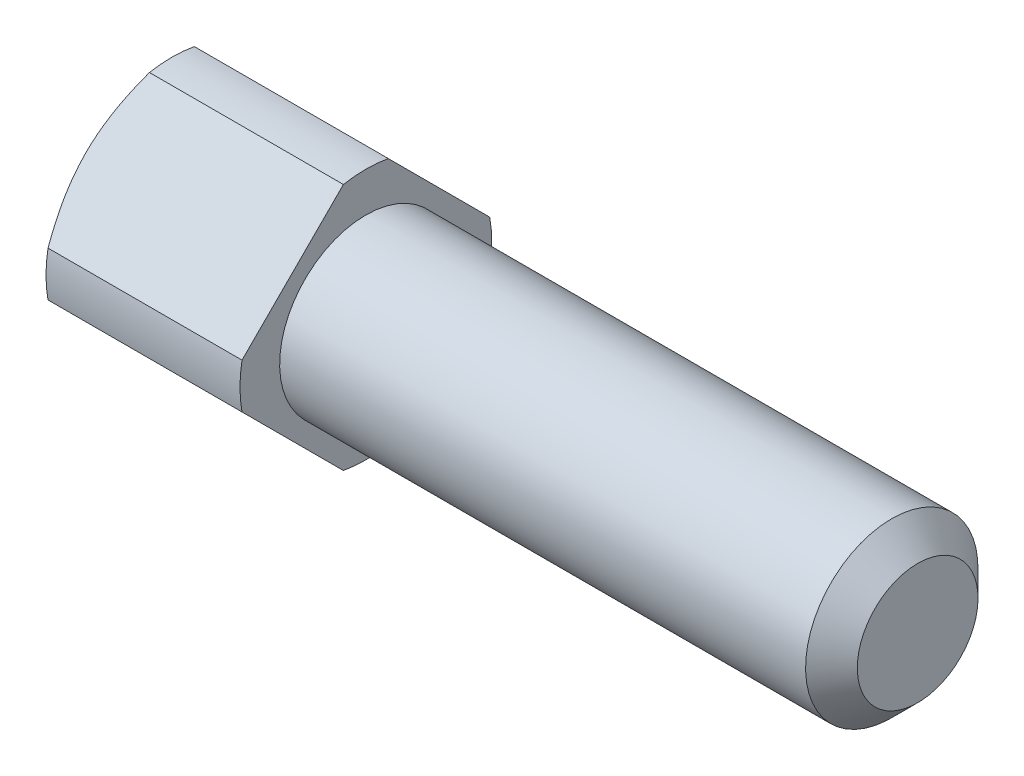
SolidWorks part; units mm, degrees
ref_plane "Front" through (0, 0, 0) normal (0, 0, 1) x (1, 0, 0)
ref_plane "Top" through (0, 0, 0) normal (0, 1, 0) x (1, 0, 0)
ref_plane "Right" through (0, 0, 0) normal (1, 0, 0) x (0, 0, -1)
sketch "Sketch1" plane through (0, 0, 0) normal (1, 0, 0) x (0, 0, -1)
  circle A0 centre (0, 0) radius 3.65
extrude "BaseHead" add sketch "Sketch1" along normal blind 6
sketch "Sketch2" plane through (0, 1.6831, -0.1205) normal (-1, 0, 0) x (0, 0, 1)
  line L1 (4.3631, -1.6831) -> (0.1205, 2.5596)
  line L2 (0.1205, 2.5596) -> (-4.1221, -1.6831)
  line L3 (-4.1221, -1.6831) -> (0.1205, -5.9257)
  line L4 (0.1205, -5.9257) -> (4.3631, -1.6831)
  circle A0 centre (0.1205, -1.6831) radius 3 construction
extrude "Cut-Extrude1" cut sketch "Sketch2" against normal blind 6 flip side to cut
sketch "Sketch3" plane through (1.2597, -5.2747, 0) normal (0, 0, 1) x (0, -1, 0)
  line L0 (-9.2897, -1.2597) -> (-8.2747, -1.2597)
  line L2 (-8.2747, -1.2597) -> (-9.2897, -0.6737)
  line L3 (-9.2897, -0.6737) -> (-9.2897, -1.2597)
  line L4 (-5.2747, 0.2856) -> (-5.2747, -6.82) construction
  line L7 (-5.9259, -1.2597) -> (-8.8662, -1.2597) construction
  dimension "D1" = 8.03
revolve "Cut-Revolve1" cut sketch "Sketch3" angle 360 about L4
sketch "Sketch4" plane through (-10.3472, 12.8472, 0) normal (0, 0, 1) x (0, -1, 0)
  line L0 (12.8472, 16.3472) -> (15.3472, 16.3472)
  line L1 (14.5972, 32.3472) -> (12.8472, 32.3472)
  line L2 (15.3472, 16.3472) -> (15.3472, 31.5972)
  line L3 (15.3472, 31.5972) -> (14.5972, 32.3472)
  line L4 (13.4984, 16.3472) -> (16.4387, 16.3472) construction
  line L5 (12.8472, 32.3472) -> (12.8472, 16.3472)
  line L6 (12.8472, 24.434) -> (12.8472, -1.2396) construction
  dimension "l" = 16
  dimension "D1" = 45
  dimension "dp" = 3.5
revolve "BaseBody" add sketch "Sketch4" angle 360 about L6
cosmetic thread "ThreadCosmetic1" [suppressed] parameters "D1"=12.8, "d"=4.5
fillet "HeadFillet" [suppressed] radius 0.2
sketch "Sketch5" plane through (0, 0, 0) normal (0, 0, 1) x (1, 0, 0)
  line L0 (9.2, 2.2835) -> (9.325, 2.5)
  line L1 (9.325, 2.5) -> (9.325, 2.75)
  line L2 (9.325, 2.75) -> (9.075, 2.75)
  line L3 (9.075, 2.75) -> (9.075, 2.5)
  line L4 (9.075, 2.5) -> (9.2, 2.2835)
  line L5 (0, 0) -> (22.608, 0) construction
  line L7 (22, -1.75) -> (22, 1.75) construction
  dimension "D1" = 5
  dimension "D2" = 0.25
  dimension "D3" = 12.8
revolve "Cut-Revolve10" [suppressed] cut sketch "Sketch5" angle 360 about L5
pattern_linear "LPattern10" [suppressed] count 43 spacing 0.3 along (1, 0, 0) of bodies 105
equation "\"d2@Sketch3\" = \"s@Sketch2\""
equation "\"D1@Sketch3\" = \"e@Sketch1\" * 1.1"
equation "\"k+c@BaseHead\" = \"k@Cut-Extrude1\""
equation "\"D1@Sketch5\" = \"d@Sketch4\""
equation "\"D2@Sketch5\" =  ( \"d@Sketch4\" - \"d@ThreadCosmetic1\" )  / 2"
equation "\"D3@LPattern10\" = \"D2@Sketch5\" * 1.2"
equation "\"D1@LPattern10\" = \"D1@ThreadCosmetic1\" / \"D3@LPattern10\""
equation "\"D3@Sketch5\" = \"D1@ThreadCosmetic1\""
